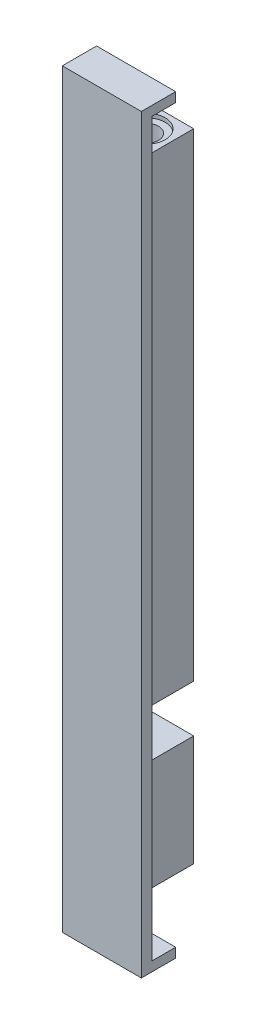
SolidWorks part; units mm, degrees
ref_plane "Front Plane" through (0, 0, 0) normal (0, 0, 1) x (1, 0, 0)
ref_plane "Top Plane" through (0, 0, 0) normal (0, 1, 0) x (1, 0, 0)
ref_plane "Right Plane" through (0, 0, 0) normal (1, 0, 0) x (0, 0, -1)
ref_plane "Plane7" through (0, -5, 0) normal (0, -1, 0) x (-1, 0, 0)
sketch "Sketch1" plane through (0, 0, 0) normal (0, 1, 0) x (1, 0, 0)
  circle A0 centre (0, 0) radius 37.5 construction
  dimension "D1" = 75
sketch "Sketch3" plane through (0, -5, 0) normal (0, -1, 0) x (1, 0, 0)
  line L0 (-3, 37.3798) -> (-3, 31.3798)
  line L1 (-3, 31.3798) -> (3, 31.3798)
  line L2 (3, 31.3798) -> (3, 37.3798)
  line L9 (0, 40.3758) -> (0, -39.6162) construction
  line L10 (0, -55) -> (0, 55) construction
  arc A0 (3, 37.3798) -> (-3, 37.3798) centre (0, 0) ccw
  circle A4 centre (0, 0) radius 37.5 construction
  dimension "D2" = 6
  dimension "D3" = 6
extrude "Boss-Extrude2" add sketch "Sketch3" along normal blind 80.5
sketch "Sketch5" plane through (0, 0, 0) normal (0, 1, 0) x (1, 0, 0)
  line L0 (-5, -38.6612) -> (-5, -39.2364)
  line L1 (5, -38.6612) -> (5, -39.666)
  line L2 (2, -38.9318) -> (2, -37.4318)
  line L3 (-2, -38.9318) -> (-2, -37.4318)
  line L12 (0, 40.7328) -> (0, -41.0085) construction
  line L13 (0, -3.3661) -> (0, 3.3661) construction
  line L14 (0, -40.0011) -> (-5, -40.0011)
  line L15 (-5, -40.0011) -> (-5, -39.2364)
  line L16 (0, -40.0011) -> (5, -40.0011)
  line L17 (5, -40.0011) -> (5, -39.666)
  arc A1 (-2, -37.4318) -> (2, -37.4318) centre (0, 0) ccw
  arc A2 (5, -38.6612) -> (2, -38.9318) centre (0, 0) cw
  arc A3 (-5, -38.6612) -> (-2, -38.9318) centre (0, 0) ccw
  circle A13 centre (0, 0) radius 37.5 construction
  dimension "D1" = 4
  dimension "D2" = 10
  dimension "D3" = 1.5
  dimension "D4" = 1.0049
  dimension "D5" = 1.0693
extrude "Boss-Extrude3" add sketch "Sketch5" against normal blind 90.5
sketch "Sketch7" plane through (0, 0, 0) normal (1, 0, 0) x (0, 0, -1)
  line L0 (0, 5.5) -> (0, -5.5) construction
  line L1 (0, -65.5) -> (-37.5, -65.5)
  line L2 (0, -65.5) -> (0, -71.5)
  line L3 (0, -71.5) -> (-37.5, -71.5)
  line L4 (-37.5, -65.5) -> (-37.5, -71.5)
  line L6 (-31.3798, -85.5) -> (-37.3798, -85.5) construction
  line L7 (0, -27.0167) -> (0, -72.0117) construction
  dimension "D1" = 37.5
  dimension "D2" = 6
  dimension "D3" = 14
revolve "Cut-Revolve1" cut sketch "Sketch7" angle 360 about L7
ref_plane "Plane5" through (0, -85.5, 0) normal (0, -1, 0) x (-1, 0, 0)
sketch "Sketch9" plane through (0, -85.5, 0) normal (0, -1, 0) x (-1, 0, 0)
  line L0 (0, -31.1751) -> (0, -37.6667) construction
  line L1 (0, 4.7417) -> (0, -4.7417) construction
  line L2 (-3.1738, -34.4209) -> (3.1592, -34.4209) construction
  circle A0 centre (0, -34.4209) radius 1.55
  dimension "D2" = 3.1
extrude "Cut-Extrude4" cut sketch "Sketch9" against normal blind 4.3
sketch "Sketch10" plane through (0, -85.5, 0) normal (0, -1, 0) x (-1, 0, 0)
  line L0 (0, -31.1751) -> (0, -37.6667) construction
  line L2 (-3.1738, -34.4209) -> (3.1592, -34.4209) construction
  circle A0 centre (0, -34.4209) radius 2.4
  dimension "D2" = 4.8
extrude "Cut-Extrude5" cut sketch "Sketch10" against normal blind 0.5
sketch "Sketch12" plane through (0, -5, 0) normal (0, -1, 0) x (-1, 0, 0)
  circle A0 centre (0, 0) radius 37.5 construction
sketch "Sketch13" plane through (0, -5, 0) normal (0, -1, 0) x (-1, 0, 0)
  line L0 (0, -31.134) -> (0, -37.6256) construction
  line L1 (-2.6479, -34.3798) -> (2.8747, -34.3798) construction
  line L2 (3, -37.3798) -> (3, -31.3798) construction
  line L3 (-3, -31.3798) -> (-3, -37.3798) construction
  circle A0 centre (0, -34.3798) radius 2.4
sketch "Sketch14" plane through (0, -5, 0) normal (0, -1, 0) x (-1, 0, 0)
  line L0 (0, -31.134) -> (0, -37.6256) construction
  line L2 (-3.1738, -34.3798) -> (3.1592, -34.3798) construction
  line L3 (3, -37.3798) -> (3, -31.3798) construction
  line L4 (-3, -31.3798) -> (-3, -37.3798) construction
  circle A0 centre (0, -34.3798) radius 1.55
  dimension "D2" = 3.1
extrude "Cut-Extrude6" cut sketch "Sketch13" along normal blind 0.5
extrude "Cut-Extrude7" cut sketch "Sketch14" along normal blind 4.3
sketch "Skizze1" plane through (0, 0, 0) normal (0, 1, 0) x (1, 0, 0)
  line L0 (-5, -40.0011) -> (5, -40.0011)
  line L1 (5, -40.0011) -> (5, -38.6612)
  line L2 (5, -38.6612) -> (-5, -38.6612)
  line L3 (-5, -38.6612) -> (-5, -40.0011)
extrude "Aufsatz-Linear austragen1" add sketch "Skizze1" along normal blind 2.2
sketch "Skizze2" plane through (0, 0, 38.6612) normal (0, 0, -1) x (-1, 0, 0)
  line L0 (-5, 2.2) -> (-5, 1)
  line L2 (-5, 1) -> (5, 1)
  line L4 (5, 1) -> (5, 2.2)
  line L5 (5, 2.2) -> (-5, 2.2)
  dimension "D1" = 1.2
extrude "Aufsatz-Linear austragen2" add sketch "Skizze2" along normal blind 3
sketch "Skizze3" plane through (0, -90.5, 0) normal (0, -1, 0) x (1, 0, 0)
  line L0 (-5, 40.0011) -> (-5, 38.6612)
  line L1 (-5, 38.6612) -> (5, 38.6612)
  line L2 (5, 38.6612) -> (5, 40.0011)
  line L3 (5, 40.0011) -> (-5, 40.0011)
extrude "Aufsatz-Linear austragen3" add sketch "Skizze3" along normal blind 2.2
sketch "Skizze4" plane through (0, 0, 38.6612) normal (0, 0, -1) x (-1, 0, 0)
  line L0 (-5, -92.7) -> (-5, -91.5)
  line L1 (-5, -92.7) -> (-5, -90.5) construction
  line L2 (-5, -91.5) -> (5, -91.5)
  line L3 (5, -92.7) -> (5, -90.5) construction
  line L4 (5, -91.5) -> (5, -92.7)
  line L5 (5, -92.7) -> (-5, -92.7)
  dimension "D1" = 1.2
extrude "Aufsatz-Linear austragen4" add sketch "Skizze4" along normal blind 3
sketch "Skizze5" [suppressed] plane through (0, 0, 31.3798) normal (0, 0, -1) x (-1, 0, 0)
  line L0 (0, -5) -> (0, -65.5)
  line L1 (3, -5) -> (-3, -5) construction
  line L2 (-3, -65.5) -> (3, -65.5) construction
  line L3 (0, -71.5) -> (0, -85.5)
  line L4 (3, -71.5) -> (-3, -71.5) construction
  line L5 (-2, -85.5) -> (2, -85.5) construction
  dimension "D1" = 60.5
  dimension "D2" = 14
